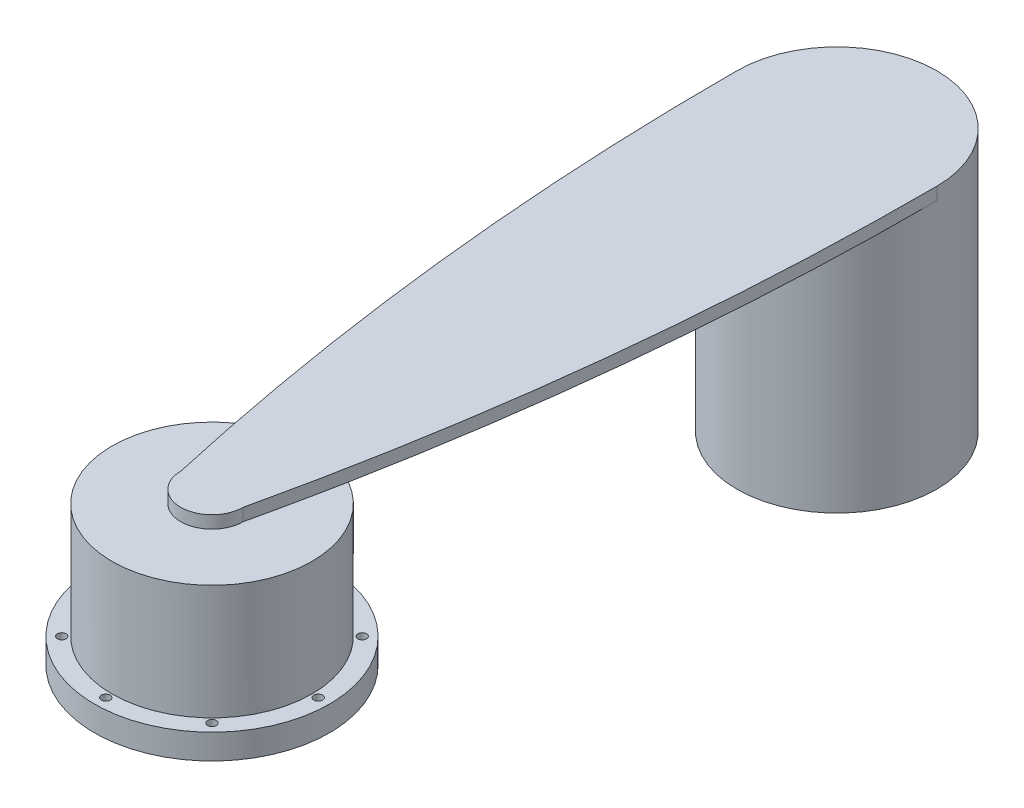
SolidWorks part; units mm, degrees
ref_plane "前视基准面" through (0, 0, 0) normal (0, 0, 1) x (1, 0, 0)
ref_plane "上视基准面" through (0, 0, 0) normal (0, 1, 0) x (1, 0, 0)
ref_plane "右视基准面" through (0, 0, 0) normal (1, 0, 0) x (0, 0, -1)
other "Configuration Table"
sketch "草图1" plane through (0, 0, 0) normal (0, 1, 0) x (1, 0, 0)
  line L0 (0, 0) -> (0, 250) construction
  circle A0 centre (0, 0) radius 40
  circle A1 centre (0, 250) radius 40
extrude "凸台-拉伸1" add sketch "草图1" along normal mid plane 100
sketch "草图2" plane through (0, 50, 0) normal (0, 1, 0) x (1, 0, 0)
  line L0 (-40, 250) -> (-40, 0)
  line L1 (40, 250) -> (39.9861, -1.0546)
  circle A0 centre (0, 250) radius 40 construction
  circle A1 centre (0, 0) radius 40 construction
  arc A2 (40, 249.9956) -> (-40, 250) centre (0, 250) ccw
  arc A3 (-40, 0) -> (39.9861, -1.0546) centre (0, 0) ccw
  circle M3 centre (0, 250) radius 40
extrude "凸台-拉伸2" add sketch "草图2" along normal blind 5 contours L0 A3 L1 M3 | M3 region at (-0.0035, 50, -93.585) region at (0, 50, -250)
sketch "草图3" plane through (0, -50, 0) normal (0, -1, 0) x (-1, 0, 0)
  line L0 (40, 0) -> (40, 250)
  line L1 (-40, 0) -> (-40, 250)
  circle A0 centre (0, 0) radius 40 construction
  circle A1 centre (0, 250) radius 40 construction
  arc A2 (-40, 0) -> (40, 0) centre (0, 0) ccw
  arc A4 (40, 250) -> (-40, 250) centre (0, 250) ccw
extrude "凸台-拉伸3" add sketch "草图3" along normal blind 5
sketch "草图4" plane through (0, 55, 0) normal (0, 1, 0) x (1, 0, 0)
  circle A0 centre (0, 0) radius 40
sketch "草图5" plane through (0, -55, 0) normal (0, -1, 0) x (1, 0, 0)
  circle A0 centre (0, 0) radius 40
extrude "凸台-拉伸4" add sketch "草图5" against normal blind 5
sketch "草图7" plane through (0, -55, 0) normal (0, -1, 0) x (1, 0, 0)
  circle A1 centre (17.25, -250) radius 2
  circle A2 centre (8.625, -264.9389) radius 2
  circle A3 centre (-8.625, -264.9389) radius 2
  circle A4 centre (-17.25, -250) radius 2
  circle A5 centre (-8.625, -235.0611) radius 2
  circle A6 centre (8.625, -235.0611) radius 2
  circle A7 centre (0, -250) radius 4
  point P17 (0, -250)
  dimension "D2" = 4
  dimension "D3" = 6
extrude "切除-拉伸2" cut sketch "草图7" against normal blind 10
sketch "草图9" plane through (0, -55, 0) normal (0, -1, 0) x (1, 0, 0)
  circle A0 centre (0, 0) radius 40
extrude "切除-拉伸4" cut sketch "草图9" against normal blind 54.05 from offset 5 offset against normal yes
sketch "草图10" plane through (0, 4.05, 0) normal (0, -1, 0) x (1, 0, 0)
  circle A0 centre (0, 0) radius 47
extrude "凸台-拉伸5" add sketch "草图10" along normal blind 10
sketch "草图11" plane through (0, -5.95, 0) normal (0, -1, 0) x (1, 0, 0)
  circle A1 centre (42.5, 0) radius 1.75
  circle A2 centre (30.052, -30.052) radius 1.75
  circle A3 centre (0, -42.5) radius 1.75
  circle A4 centre (-30.052, -30.052) radius 1.75
  circle A5 centre (-42.5, 0) radius 1.75
  circle A6 centre (-30.052, 30.052) radius 1.75
  circle A7 centre (0, 42.5) radius 1.75
  circle A8 centre (30.052, 30.052) radius 1.75
  point P21 (0, 0)
  dimension "D1" = 3.5
  dimension "D2" = 8
extrude "切除-拉伸5" cut sketch "草图11" against normal up to next
sketch "草图12" plane through (0, 55, 0) normal (0, 1, 0) x (1, 0, 0)
  circle A0 centre (0, 250) radius 40
extrude "切除-拉伸6" cut sketch "草图12" against normal blind 20 from offset 80 offset against normal yes
sketch "草图13" plane through (0, -25, 0) normal (0, -1, 0) x (1, 0, 0)
  circle A0 centre (0, -250) radius 40
sketch "草图14" plane through (0, 50, 0) normal (0, -1, 0) x (1, 0, 0)
  circle A0 centre (0, -250) radius 40
extrude "凸台-拉伸6" add sketch "草图14" against normal blind 5
sketch "草图15" plane through (0, -55, 0) normal (0, -1, 0) x (1, 0, 0)
  line L0 (0, 0) -> (0, -250) construction
  line L1 (40, 0) -> (40, -250)
  line L2 (-40, 0) -> (-40, -250)
  arc A0 (40, 0) -> (-40, 0) centre (0, 0) ccw
  arc A1 (-40, -250) -> (40, -250) centre (0, -250) ccw
  point P4 (0, -125)
extrude "切除-拉伸8" cut sketch "草图15" against normal blind 10
sketch "草图17" plane through (0, 55, 0) normal (0, 1, 0) x (1, 0, 0)
  line L0 (0, 0) -> (0, 250) construction
  line L1 (-40, 0) -> (-40, 250)
  line L2 (40, 0) -> (40, 250)
  arc A0 (-40, 0) -> (40, 0) centre (0, 0) ccw
  arc A1 (40, 250) -> (-40, 250) centre (0, 250) ccw
  point P3 (0, 125)
extrude "切除-拉伸9" cut sketch "草图17" against normal blind 5
ref_plane "基准面2" through (0, 55, 0) normal (0, 1, 0) x (1, 0, 0)
sketch "草图18" plane through (0, 55, 0) normal (0, 1, 0) x (1, 0, 0)
  line L0 (0, 250) -> (0, 0) construction
  arc A0 (40, 250) -> (-40, 250) centre (0, 250) ccw
  arc A1 (-12.5, 0) -> (12.5, 0) centre (0, 0) ccw
  arc A2 (-40, 250) -> (-12.5, 0) centre (1080.4349, 246.7353) ccw
  arc A3 (40, 250) -> (12.5, 0) centre (-1080.4349, 246.7353) cw
  dimension "D1" = 25
extrude "凸台-拉伸8" add sketch "草图18" against normal blind 5
extrude "拉伸-薄壁1" add sketch "草图13" along normal blind 25 thin thin type one direction reverse wall 10
